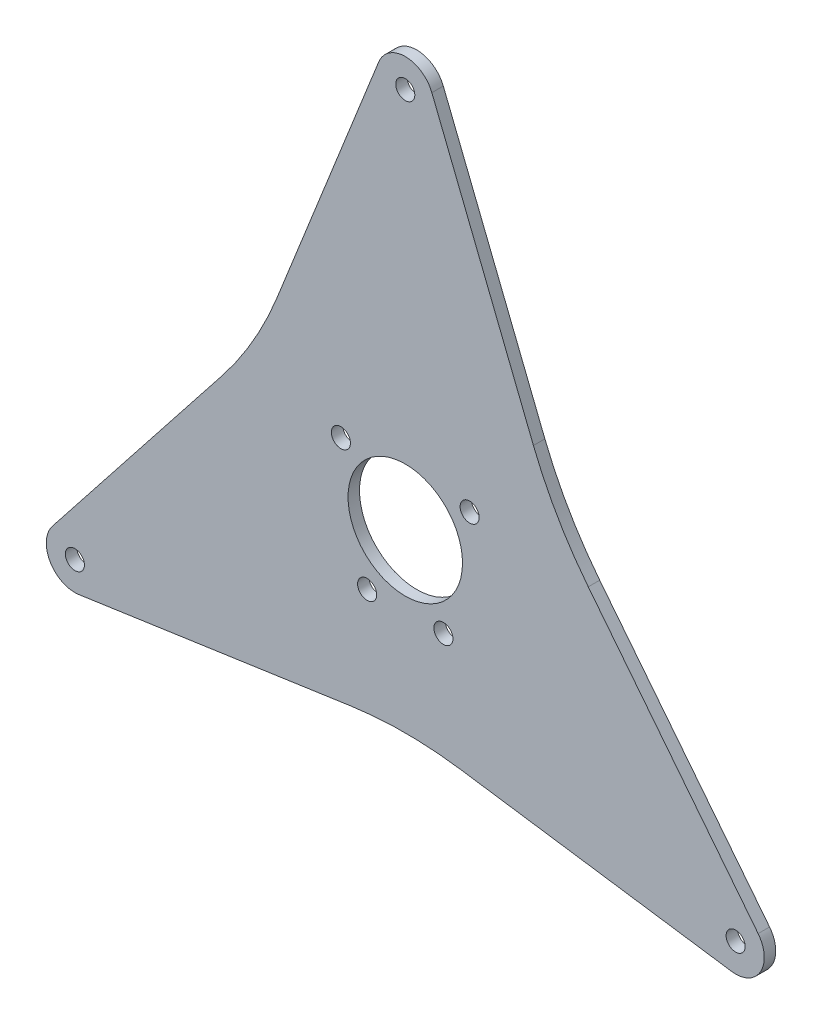
SolidWorks part; units mm, degrees
ref_plane "Front Plane" through (0, 0, 0) normal (0, 0, 1) x (1, 0, 0)
ref_plane "Top Plane" through (0, 0, 0) normal (0, 1, 0) x (1, 0, 0)
ref_plane "Right Plane" through (0, 0, 0) normal (1, 0, 0) x (0, 0, -1)
sketch "Sketch1" plane through (0, 0, 0) normal (0, 0, 1) x (1, 0, 0)
  line L0 (33.75, 25.0611) -> (-33.75, 25.0611) construction
  line L1 (0, 0) -> (0, 51.7411) construction
  line L2 (-184.9825, -90.7107) -> (-95.9322, 22.1916)
  line L3 (-67.1846, 71.9839) -> (-13.9335, 205.5549)
  line L4 (13.9335, 205.5549) -> (67.1846, 71.9839)
  line L5 (95.9322, 22.1916) -> (184.9825, -90.7107)
  line L6 (0, 0) -> (-81.3002, 46.9387) construction
  line L7 (-171.049, -114.8442) -> (-28.7476, -94.1755)
  line L8 (28.7476, -94.1755) -> (171.049, -114.8442)
  line L9 (-33.75, 25.0611) -> (20, -36.9324) construction
  line L10 (-20, -36.9324) -> (20, -36.9324) construction
  line L11 (33.75, 25.0611) -> (-20, -36.9324) construction
  line L12 (0, 0) -> (-20, -36.9324) construction
  circle A0 centre (0, 200) radius 5
  circle A1 centre (173.2051, -100) radius 5
  circle A2 centre (-173.2051, -100) radius 5
  circle A7 centre (0, 0) radius 30
  arc A8 (13.9335, 205.5549) -> (-13.9335, 205.5549) centre (0, 200) ccw
  arc A9 (171.049, -114.8442) -> (184.9825, -90.7107) centre (173.2051, -100) ccw
  arc A10 (-184.9825, -90.7107) -> (-171.049, -114.8442) centre (-173.2051, -100) ccw
  arc A11 (67.1846, 71.9839) -> (95.9322, 22.1916) centre (252.9648, 146.0493) ccw
  arc A12 (-95.9322, 22.1916) -> (-67.1846, 71.9839) centre (-252.9648, 146.0493) ccw
  arc A13 (-28.7476, -94.1755) -> (28.7476, -94.1755) centre (0, -292.0986) cw
  circle A14 centre (0, 0) radius 67 construction
  circle A15 centre (-33.75, 25.0611) radius 5
  circle A16 centre (33.75, 25.0611) radius 5
  circle A17 centre (-20, -36.9324) radius 5
  circle A18 centre (20, -36.9324) radius 5
  point P2 (0, 25.0611)
  point P10 (0, 0)
  point P21 (0, 0)
  point P30 (0, -90)
  point P40 (77.9423, 45)
  point P43 (-77.9423, 45)
  point P51 (0, -36.9324)
  dimension "D1" = 10
  dimension "D4" = 42
  dimension "D8" = 60
  dimension "D9" = 30
  dimension "D11" = 200
  dimension "D12" = 200
  dimension "D15" = 10
  dimension "D2" = 200
  dimension "D10" = 60
  dimension "D13" = 90
  dimension "D14" = 90
  dimension "D16" = 67.5
  dimension "D17" = 40
  dimension "D18" = 63.5
  dimension "D3" = 3
extrude "Boss-Extrude1" add sketch "Sketch1" along normal blind 6
